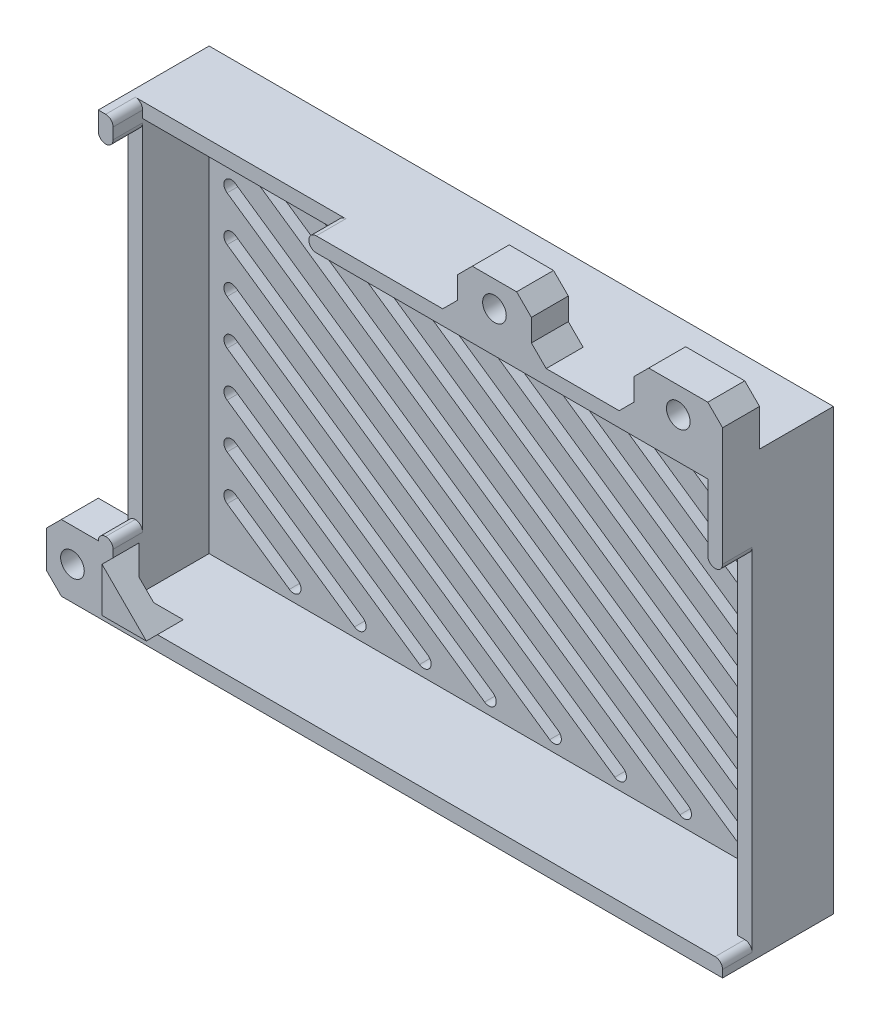
SolidWorks part; units mm, degrees
ref_plane "前视基准面" through (0, 0, 0) normal (0, 0, 1) x (1, 0, 0)
ref_plane "上视基准面" through (0, 0, 0) normal (0, 1, 0) x (1, 0, 0)
ref_plane "右视基准面" through (0, 0, 0) normal (1, 0, 0) x (0, 0, -1)
sketch "草图1" plane through (0, 0, 0) normal (0, 0, 1) x (1, 0, 0)
  line L1 (0, 0) -> (84.5, 0)
  line L2 (0, 0) -> (0, 59.5)
  line L3 (0, 59.5) -> (84.5, 59.5)
  line L4 (84.5, 0) -> (84.5, 59.5)
  dimension "D1" = 59.5
  dimension "D2" = 84.5
extrude "凸台-拉伸1" add sketch "草图1" along normal blind 2
sketch "草图2" plane through (0, 0, 2) normal (0, 0, 1) x (1, 0, 0)
  line L0 (82.5, 57.5) -> (2, 57.5)
  line L1 (2, 57.5) -> (2, 2)
  line L2 (2, 2) -> (82.5, 2)
  line L3 (82.5, 2) -> (82.5, 57.5)
  line L4 (0, 59.5) -> (0, 0)
  line L5 (0, 0) -> (84.5, 0)
  line L6 (84.5, 0) -> (84.5, 59.5)
  line L7 (84.5, 59.5) -> (0, 59.5)
  line L8 (0, 59.5) -> (0, 0)
  line L9 (0, 0) -> (84.5, 0)
  line L10 (84.5, 0) -> (84.5, 59.5)
  line L11 (84.5, 59.5) -> (0, 59.5)
  dimension "D1" = 0
  dimension "D2" = 2
extrude "凸台-拉伸2" add sketch "草图2" along normal blind 13
sketch "草图3" plane through (0, 59.5, 0) normal (0, 1, 0) x (1, 0, 0)
  line L0 (84.5, -15) -> (0, -15) construction
  line L1 (2, -15) -> (28.5, -15)
  line L2 (2, -15) -> (2, -11)
  line L3 (2, -11) -> (28.5, -11)
  line L4 (28.5, -15) -> (28.5, -11)
  line L5 (0, -15) -> (0, 0) construction
  dimension "D1" = 2
  dimension "D2" = 26.5
  dimension "D3" = 4
extrude "切除-拉伸1" cut sketch "草图3" against normal up to surface (2 mm away) up to face at (42.25, 57.5, 8.5)
sketch "草图4" plane through (0, 0, 0) normal (-1, 0, 0) x (0, 0, 1)
  line L0 (15, 59.5) -> (15, 0) construction
  line L1 (15, 10) -> (11, 10)
  line L2 (15, 10) -> (15, 56)
  line L3 (15, 56) -> (11, 56)
  line L4 (11, 10) -> (11, 56)
  line L5 (15, 59.5) -> (0, 59.5) construction
  dimension "D1" = 3.5
  dimension "D2" = 46
  dimension "D3" = 4
extrude "切除-拉伸2" cut sketch "草图4" against normal up to surface (2 mm away) up to face at (2, 39.6667, 9.3333)
sketch "草图5" plane through (84.5, 0, 0) normal (1, 0, 0) x (0, 0, -1)
  line L0 (-15, 0) -> (-15, 59.5) construction
  line L1 (-15, 2) -> (-11, 2)
  line L2 (-15, 2) -> (-15, 47.5)
  line L3 (-15, 47.5) -> (-11, 47.5)
  line L4 (-11, 2) -> (-11, 47.5)
  line L5 (-15, 0) -> (0, 0) construction
  dimension "D1" = 45.5
  dimension "D2" = 2
  dimension "D3" = 4
extrude "切除-拉伸3" cut sketch "草图5" against normal up to surface (2 mm away) up to face at (82.5, 29.75, 8.5)
sketch "草图6" plane through (0, 0, 2) normal (0, 0, 1) x (1, 0, 0)
  line L0 (2, 57.5) -> (82.5, 2) construction
  line L1 (2, 57.5) -> (2, 2) construction
  line L2 (5, 55.4317) -> (79.5, 55.4317) construction
  line L3 (5, 55.4317) -> (5, 4.0683) construction
  line L4 (5, 4.0683) -> (79.5, 4.0683) construction
  line L5 (79.5, 55.4317) -> (79.5, 4.0683) construction
  line L6 (82.5, 2) -> (82.5, 57.5) construction
  line L7 (5, 15.9562) -> (22.2427, 4.0683) construction
  line L8 (5.5676, 16.7795) -> (22.8103, 4.8916)
  line L9 (4.4324, 15.1329) -> (21.6751, 3.245)
  line L10 (5, 22.0293) -> (31.0515, 4.0683) construction
  line L11 (5.5676, 22.8526) -> (31.6191, 4.8916)
  line L12 (4.4324, 21.206) -> (30.4839, 3.245)
  line L13 (5, 28.1025) -> (39.8603, 4.0683) construction
  line L14 (5.5676, 28.9258) -> (40.428, 4.8916)
  line L15 (4.4324, 27.2792) -> (39.2927, 3.245)
  line L16 (5, 34.1756) -> (48.6692, 4.0683) construction
  line L17 (5.5676, 34.9989) -> (49.2368, 4.8916)
  line L18 (4.4324, 33.3523) -> (48.1015, 3.245)
  line L19 (5, 40.2488) -> (57.478, 4.0683) construction
  line L20 (5.5676, 41.0721) -> (58.0456, 4.8916)
  line L21 (4.4324, 39.4255) -> (56.9104, 3.245)
  line L22 (5, 46.3219) -> (66.2868, 4.0683) construction
  line L23 (5.5676, 47.1452) -> (66.8544, 4.8916)
  line L24 (4.4324, 45.4986) -> (65.7192, 3.245)
  line L25 (9.4044, 55.4317) -> (79.5, 7.1049) construction
  line L26 (9.972, 56.255) -> (80.0676, 7.9282)
  line L27 (8.8368, 54.6084) -> (78.9324, 6.2816)
  line L28 (5, 52.3951) -> (75.0956, 4.0683) construction
  line L29 (5.5676, 53.2184) -> (75.6632, 4.8916)
  line L30 (4.4324, 51.5718) -> (74.528, 3.245)
  line L31 (5, 9.883) -> (13.4339, 4.0683) construction
  line L32 (5.5676, 10.7063) -> (14.0015, 4.8916)
  line L33 (4.4324, 9.0597) -> (12.8663, 3.245)
  line L34 (18.2132, 55.4317) -> (79.5, 13.1781) construction
  line L35 (18.7808, 56.255) -> (80.0676, 14.0014)
  line L36 (17.6456, 54.6084) -> (78.9324, 12.3548)
  line L37 (27.022, 55.4317) -> (79.5, 19.2512) construction
  line L38 (27.5896, 56.255) -> (80.0676, 20.0745)
  line L39 (26.4544, 54.6084) -> (78.9324, 18.4279)
  line L40 (35.8308, 55.4317) -> (79.5, 25.3244) construction
  line L41 (36.3985, 56.255) -> (80.0676, 26.1477)
  line L42 (35.2632, 54.6084) -> (78.9324, 24.5011)
  line L43 (44.6397, 55.4317) -> (79.5, 31.3975) construction
  line L44 (45.2073, 56.255) -> (80.0676, 32.2208)
  line L45 (44.072, 54.6084) -> (78.9324, 30.5742)
  line L46 (53.4485, 55.4317) -> (79.5, 37.4707) construction
  line L47 (54.0161, 56.255) -> (80.0676, 38.294)
  line L48 (52.8809, 54.6084) -> (78.9324, 36.6474)
  line L49 (62.2573, 55.4317) -> (79.5, 43.5438) construction
  line L50 (62.8249, 56.255) -> (80.0676, 44.3671)
  line L51 (61.6897, 54.6084) -> (78.9324, 42.7205)
  line L52 (71.0661, 55.4317) -> (79.5, 49.617) construction
  line L53 (71.6337, 56.255) -> (80.0676, 50.4403)
  line L54 (70.4985, 54.6084) -> (78.9324, 48.7937)
  arc A0 (5.5676, 16.7795) -> (4.4324, 15.1329) centre (5, 15.9562) ccw
  arc A1 (21.6751, 3.245) -> (22.8103, 4.8916) centre (22.2427, 4.0683) ccw
  arc A2 (5.5676, 22.8526) -> (4.4324, 21.206) centre (5, 22.0293) ccw
  arc A3 (30.4839, 3.245) -> (31.6191, 4.8916) centre (31.0515, 4.0683) ccw
  arc A4 (5.5676, 28.9258) -> (4.4324, 27.2792) centre (5, 28.1025) ccw
  arc A5 (39.2927, 3.245) -> (40.428, 4.8916) centre (39.8603, 4.0683) ccw
  arc A6 (5.5676, 34.9989) -> (4.4324, 33.3523) centre (5, 34.1756) ccw
  arc A7 (48.1015, 3.245) -> (49.2368, 4.8916) centre (48.6692, 4.0683) ccw
  arc A8 (5.5676, 41.0721) -> (4.4324, 39.4255) centre (5, 40.2488) ccw
  arc A9 (56.9104, 3.245) -> (58.0456, 4.8916) centre (57.478, 4.0683) ccw
  arc A10 (5.5676, 47.1452) -> (4.4324, 45.4986) centre (5, 46.3219) ccw
  arc A11 (65.7192, 3.245) -> (66.8544, 4.8916) centre (66.2868, 4.0683) ccw
  arc A12 (9.972, 56.255) -> (8.8368, 54.6084) centre (9.4044, 55.4317) ccw
  arc A13 (78.9324, 6.2816) -> (80.0676, 7.9282) centre (79.5, 7.1049) ccw
  arc A14 (5.5676, 53.2184) -> (4.4324, 51.5718) centre (5, 52.3951) ccw
  arc A15 (74.528, 3.245) -> (75.6632, 4.8916) centre (75.0956, 4.0683) ccw
  arc A16 (5.5676, 10.7063) -> (4.4324, 9.0597) centre (5, 9.883) ccw
  arc A17 (12.8663, 3.245) -> (14.0015, 4.8916) centre (13.4339, 4.0683) ccw
  arc A18 (18.7808, 56.255) -> (17.6456, 54.6084) centre (18.2132, 55.4317) ccw
  arc A19 (78.9324, 12.3548) -> (80.0676, 14.0014) centre (79.5, 13.1781) ccw
  arc A20 (27.5896, 56.255) -> (26.4544, 54.6084) centre (27.022, 55.4317) ccw
  arc A21 (78.9324, 18.4279) -> (80.0676, 20.0745) centre (79.5, 19.2512) ccw
  arc A22 (36.3985, 56.255) -> (35.2632, 54.6084) centre (35.8308, 55.4317) ccw
  arc A23 (78.9324, 24.5011) -> (80.0676, 26.1477) centre (79.5, 25.3244) ccw
  arc A24 (45.2073, 56.255) -> (44.072, 54.6084) centre (44.6397, 55.4317) ccw
  arc A25 (78.9324, 30.5742) -> (80.0676, 32.2208) centre (79.5, 31.3975) ccw
  arc A26 (54.0161, 56.255) -> (52.8809, 54.6084) centre (53.4485, 55.4317) ccw
  arc A27 (78.9324, 36.6474) -> (80.0676, 38.294) centre (79.5, 37.4707) ccw
  arc A28 (62.8249, 56.255) -> (61.6897, 54.6084) centre (62.2573, 55.4317) ccw
  arc A29 (78.9324, 42.7205) -> (80.0676, 44.3671) centre (79.5, 43.5438) ccw
  arc A30 (71.6337, 56.255) -> (70.4985, 54.6084) centre (71.0661, 55.4317) ccw
  arc A31 (78.9324, 48.7937) -> (80.0676, 50.4403) centre (79.5, 49.617) ccw
  point P14 (13.6214, 10.0122)
  point P21 (18.0258, 13.0488)
  point P26 (22.4302, 16.0854)
  point P33 (26.8346, 19.122)
  point P40 (31.239, 22.1586)
  point P47 (35.6434, 25.1951)
  point P54 (44.4522, 31.2683)
  point P63 (40.0478, 28.2317)
  point P70 (9.217, 6.9757)
  point P77 (48.8566, 34.3049)
  point P82 (53.261, 37.3414)
  point P89 (57.6654, 40.378)
  point P96 (62.0698, 43.4146)
  point P103 (66.4742, 46.4512)
  point P110 (70.8786, 49.4878)
  point P117 (75.283, 52.5243)
  dimension "D3" = 1
  dimension "D4" = 1
  dimension "D5" = 1
  dimension "D6" = 1
  dimension "D7" = 1
  dimension "D8" = 1
  dimension "D14" = 1
  dimension "D17" = 1
  dimension "D19" = 1
  dimension "D20" = 1
  dimension "D21" = 1
  dimension "D22" = 1
  dimension "D23" = 1
  dimension "D24" = 1
  dimension "D25" = 1
  dimension "D33" = 1
  dimension "D34" = 5
  dimension "D1" = 3
  dimension "D2" = 3
  dimension "D9" = 5
  dimension "D10" = 5
  dimension "D11" = 5
  dimension "D12" = 5
  dimension "D13" = 5
  dimension "D15" = 5
  dimension "D16" = 2.5
  dimension "D18" = 5
  dimension "D26" = 2.5
  dimension "D27" = 5
  dimension "D28" = 5
  dimension "D29" = 5
  dimension "D30" = 5
  dimension "D31" = 5
  dimension "D32" = 5
extrude "切除-拉伸4" cut sketch "草图6" against normal through all
sketch "草图9" plane through (0, 0, 15) normal (0, 0, 1) x (1, 0, 0)
  line L0 (-7, 4.5) -> (10.1004, 4.5) construction
  line L1 (0, 0) -> (-7, 0)
  line L2 (0, 0) -> (0, 9)
  line L3 (0, 9) -> (-7, 9)
  line L4 (-7, 0) -> (-7, 9)
  line L5 (-3.5, 0) -> (-3.5, 18.1576) construction
  circle A0 centre (-3.5, 4.5) radius 1.6
  dimension "D3" = 3.2
  dimension "D1" = 7
  dimension "D2" = 9
extrude "凸台-拉伸5" add sketch "草图9" against normal blind 5
fillet "圆角1" radius 1 10 edges at (2, 10, 13) (84.5, 47.5, 13) (82.5, 47.5, 13) (84.5, 2, 13) (28.5, 57.5, 13) (28.5, 59.5, 13) (2, 59.5, 13) (2, 56, 13) (0, 56, 13) (0, 10, 13)
ref_plane "基准面1" through (0, 0, 12.5) normal (0, 0, 1) x (1, 0, 0)
sketch "草图14" plane through (0, 0, 12.5) normal (0, 0, 1) x (1, 0, 0)
  line L0 (82.5, 57.5) -> (29.5, 57.5) construction
  line L1 (54.5, 57.5) -> (52.5, 57.5)
  line L2 (54.5, 57.5) -> (54.5, 55.5)
  line L3 (54.5, 55.5) -> (52.5, 55.5)
  line L4 (52.5, 57.5) -> (52.5, 55.5)
  line L5 (82.5, 57.5) -> (29.5, 57.5) construction
  line L6 (82.5, 2) -> (82.5, 48.5) construction
  dimension "D1" = 28
  dimension "D2" = 30
  dimension "D3" = 2
extrude "凸台-拉伸7" [suppressed] add sketch "草图14" against normal blind 1.3
chamfer "倒角3" [suppressed] distance 1 angle 45
fillet "圆角2" [suppressed] radius 1
ref_plane "基准面2" through (0, 0, 16.5) normal (0, 0, 1) x (1, 0, 0)
sketch "草图15" plane through (0, 0, 16.5) normal (0, 0, 1) x (1, 0, 0)
  line L0 (2, 2) -> (83.5, 2) construction
  line L1 (2, 9) -> (2, 2) construction
  line L2 (2, 2) -> (83.5, 2) construction
  line L3 (2, 9) -> (2, 2) construction
  line L4 (2, 2) -> (2, 8)
  line L5 (2, 8) -> (8, 2)
  line L6 (8, 2) -> (2, 2)
  dimension "D1" = 6
  dimension "D2" = 6
extrude "凸台-拉伸8" add sketch "草图15" against normal blind 3
chamfer "倒角4" distance 2 angle 45 2 edges at (5, 2, 13.5) (2, 5, 13.5)
sketch "草图16" plane through (0, 0, 15) normal (0, 0, 1) x (1, 0, 0)
  line L0 (72.5, 63) -> (84.5, 63) construction
  line L1 (84.5, 59.5) -> (72.5, 59.5)
  line L2 (84.5, 59.5) -> (84.5, 66.5)
  line L3 (84.5, 66.5) -> (72.5, 66.5)
  line L4 (72.5, 59.5) -> (72.5, 66.5)
  line L5 (78.5, 66.5) -> (78.5, 59.5) construction
  line L6 (84.5, 59.5) -> (29.5, 59.5) construction
  line L7 (58.62, 59.5) -> (48.62, 59.5)
  line L8 (58.62, 59.5) -> (58.62, 66.5)
  line L9 (58.62, 66.5) -> (48.62, 66.5)
  line L10 (48.62, 59.5) -> (48.62, 66.5)
  line L11 (48.62, 63) -> (58.62, 63) construction
  line L12 (53.62, 66.5) -> (53.62, 59.5) construction
  circle A0 centre (78.5, 63) radius 1.6
  circle A1 centre (53.62, 63) radius 1.6
  dimension "D3" = 3.2
  dimension "D6" = 3.2
  dimension "D1" = 12
  dimension "D2" = 7
  dimension "D4" = 10
  dimension "D5" = 7
  dimension "D7" = 24.88
extrude "凸台-拉伸9" add sketch "草图16" against normal blind 5
chamfer "倒角5" distance 2 angle 45 9 edges at (-7, 0, 12.5) (-7, 9, 12.5) (48.62, 59.5, 12.5) (48.62, 66.5, 12.5) (72.5, 59.5, 12.5) (58.62, 59.5, 12.5) (58.62, 66.5, 12.5) (72.5, 66.5, 12.5) (84.5, 66.5, 12.5)
